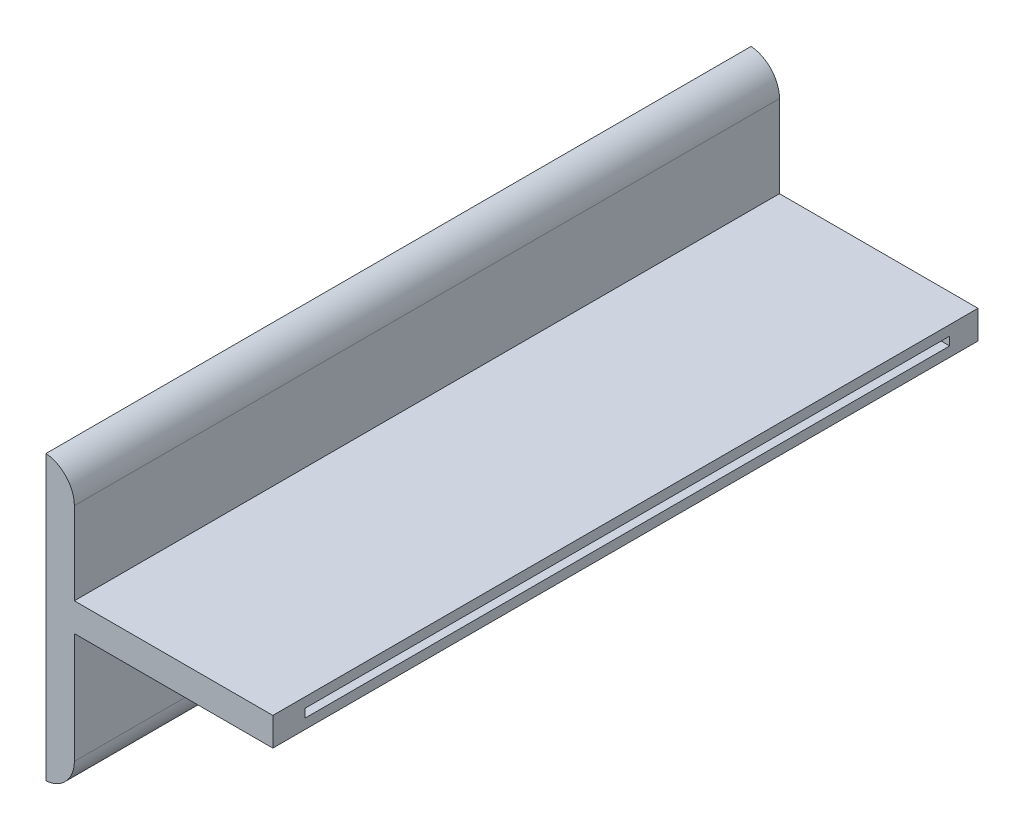
SolidWorks part; units mm, degrees
ref_plane "Front Plane" through (0, 0, 0) normal (0, 0, 1) x (1, 0, 0)
ref_plane "Top Plane" through (0, 0, 0) normal (0, 1, 0) x (1, 0, 0)
ref_plane "Right Plane" through (0, 0, 0) normal (1, 0, 0) x (0, 0, -1)
sketch "Sketch1" plane through (0, 0, 0) normal (1, 0, 0) x (0, 0, -1)
  line L1 (-7.0202, 4.053) -> (241.6598, 4.053)
  line L2 (-7.0202, 4.053) -> (-7.0202, -5.947)
  line L3 (-7.0202, -5.947) -> (241.6598, -5.947)
  line L4 (241.6598, 4.053) -> (241.6598, -5.947)
  dimension "D1" = 10
  dimension "D2" = 248.68
extrude "Boss-Extrude1" add sketch "Sketch1" along normal blind 80
sketch "Sketch3" plane through (0, 4.053, 0) normal (0, 1, 0) x (1, 0, 0)
  line L0 (80, -7.0202) -> (0, -7.0202) construction
  line L1 (0, 241.6598) -> (10, 241.6598)
  line L2 (0, 241.6598) -> (0, -7.0202)
  line L3 (0, -7.0202) -> (10, -7.0202)
  line L4 (10, 241.6598) -> (10, -7.0202)
extrude "Boss-Extrude2" add sketch "Sketch3" along normal blind 40
ref_plane "Plane1" through (10, 44.053, -241.6598) normal (-1, 0, 0) x (0, 0, 1)
sketch "Sketch5" plane through (0, -5.947, 0) normal (0, -1, 0) x (1, 0, 0)
  line L0 (10, -238.9098) -> (10, -244.4098) construction
  line L1 (0, 7.0202) -> (10, 7.0202)
  line L2 (0, 7.0202) -> (0, -241.6598)
  line L3 (0, -241.6598) -> (10, -241.6598)
  line L4 (10, 7.0202) -> (10, -241.6598)
  line L5 (80, -241.6598) -> (0, -241.6598) construction
extrude "Boss-Extrude3" add sketch "Sketch5" along normal blind 50
fillet "Fillet1" radius 11 1 edges at (10, 44.053, -117.3198)
fillet "Fillet2" radius 11 1 edges at (10, -55.947, -117.3198)
sketch "Sketch6" plane through (80, 0, 0) normal (1, 0, 0) x (0, 0, -1)
  line L0 (-7.0202, -0.947) -> (2.9798, -0.947) construction
  line L1 (-7.0202, 4.053) -> (-7.0202, -5.947) construction
  line L2 (241.6598, -0.947) -> (231.6598, -0.947) construction
  line L3 (241.6598, -5.947) -> (241.6598, 4.053) construction
  line L4 (231.6598, -0.947) -> (231.6598, 0.553) construction
  line L5 (231.6598, -0.947) -> (231.6598, -2.447) construction
  line L7 (231.6598, 0.553) -> (4.2433, 0.553)
  line L8 (231.6598, 0.553) -> (231.6598, -2.447)
  line L9 (231.6598, -2.447) -> (4.2433, -2.447)
  line L10 (4.2433, 0.553) -> (4.2433, -2.447)
extrude "Cut-Extrude2" cut sketch "Sketch6" against normal blind 70
